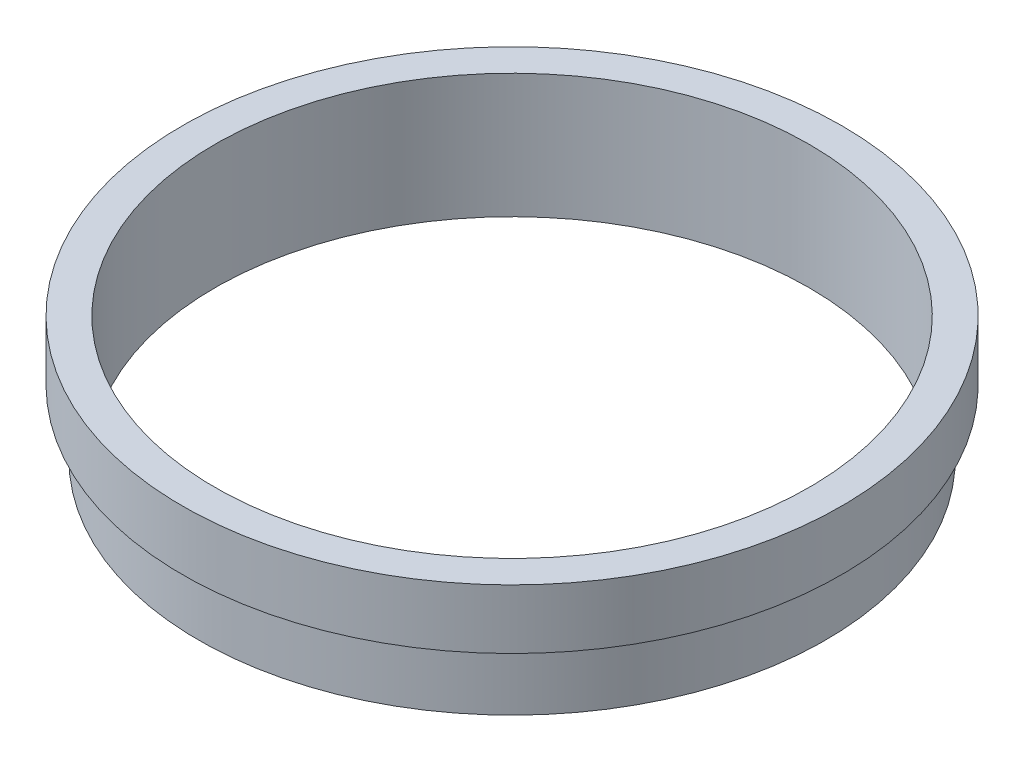
SolidWorks part; units mm, degrees
ref_plane "Front Plane" through (0, 0, 0) normal (0, 0, 1) x (1, 0, 0)
ref_plane "Top Plane" through (0, 0, 0) normal (0, 1, 0) x (1, 0, 0)
ref_plane "Right Plane" through (0, 0, 0) normal (1, 0, 0) x (0, 0, -1)
sketch "Sketch1" plane through (0, 0, 0) normal (0, 0, 1) x (1, 0, 0)
  line L0 (0, 0) -> (0, 20)
  line L2 (27.5, 0) -> (29, 0)
  line L3 (27.5, 0) -> (27.5, 11.5)
  line L4 (27.5, 11.5) -> (29, 11.5)
  line L5 (29, 0) -> (29, 11.5)
  line L6 (29, 11.5) -> (30.5, 11.5)
  line L7 (29, 11.5) -> (29, 6)
  line L8 (29, 6) -> (30.5, 6)
  line L9 (30.5, 11.5) -> (30.5, 6)
  dimension "D1" = 11.5
  dimension "D2" = 27.5
  dimension "D3" = 1.5
  dimension "D4" = 1.5
  dimension "D5" = 5.5
revolve "Revolve1" add sketch "Sketch1" angle 360 about L0 region at (28.25, 5.75, 0) region at (29.75, 8.75, 0)
